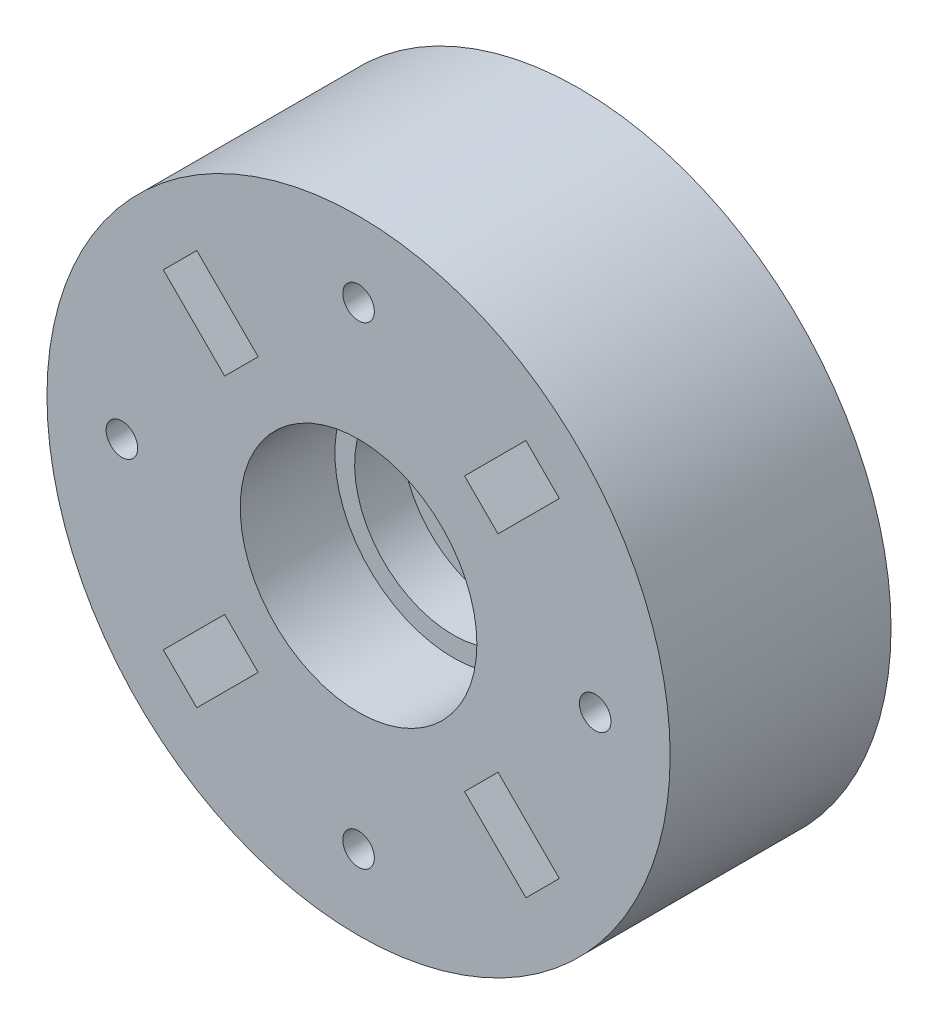
SolidWorks part; units mm, degrees
ref_plane "Alzado" through (0, 0, 0) normal (0, 0, 1) x (1, 0, 0)
ref_plane "Planta" through (0, 0, 0) normal (0, 1, 0) x (1, 0, 0)
ref_plane "Vista lateral" through (0, 0, 0) normal (1, 0, 0) x (0, 0, -1)
sketch "Croquis1" plane through (0, 0, 0) normal (0, 0, 1) x (1, 0, 0)
  line L0 (0, 50.6458) -> (0, -51.1293) construction
  circle A0 centre (0, 0) radius 39.5
  circle A1 centre (0, 0) radius 12.5
  circle A2 centre (0, 30) radius 2
  circle A3 centre (30, 0) radius 2
  circle A4 centre (0, -30) radius 2
  circle A5 centre (-30, 0) radius 2
  point P17 (0, 0)
  dimension "D1" = 79
  dimension "D2" = 25
  dimension "D4" = 4
  dimension "D3" = 30
  dimension "D5" = 4
extrude "Saliente-Extruir1" add sketch "Croquis1" along normal blind 28
sketch "Croquis3" plane through (0, 0, 28) normal (0, 0, 1) x (1, 0, 0)
  line L0 (0, 0) -> (28.2843, 28.2843) construction
  line L1 (0, 0) -> (39.5, 0) construction
  line L2 (17.6777, 13.435) -> (25.4558, 21.2132)
  line L3 (17.6777, 13.435) -> (13.435, 17.6777)
  line L4 (25.4558, 21.2132) -> (21.2132, 25.4558)
  line L5 (13.435, 17.6777) -> (21.2132, 25.4558)
  line L6 (17.6777, 13.435) -> (21.2132, 25.4558) construction
  line L7 (25.4558, 21.2132) -> (13.435, 17.6777) construction
  line L8 (13.435, -16.9706) -> (21.2132, -24.7487)
  line L9 (13.435, -16.9706) -> (17.6777, -12.7279)
  line L10 (17.6777, -12.7279) -> (25.4558, -20.5061)
  line L11 (21.2132, -24.7487) -> (25.4558, -20.5061)
  line L12 (-16.9706, -12.7279) -> (-24.7487, -20.5061)
  line L13 (-16.9706, -12.7279) -> (-12.7279, -16.9706)
  line L14 (-12.7279, -16.9706) -> (-20.5061, -24.7487)
  line L15 (-24.7487, -20.5061) -> (-20.5061, -24.7487)
  line L16 (-12.7279, 17.6777) -> (-20.5061, 25.4558)
  line L17 (-12.7279, 17.6777) -> (-16.9706, 13.435)
  line L18 (-16.9706, 13.435) -> (-24.7487, 21.2132)
  line L19 (-20.5061, 25.4558) -> (-24.7487, 21.2132)
  circle A0 centre (0, 0) radius 39.5 construction
  circle A1 centre (0, 0) radius 15
  point P8 (19.4454, 19.4454)
  point P27 (0.3536, 0.3536)
  dimension "D9" = 30
  dimension "D1" = 40
  dimension "D2" = 45
  dimension "D3" = 3
  dimension "D4" = 3
  dimension "D5" = 11
  dimension "D6" = 27.5
  dimension "D7" = 6
  dimension "D8" = 4
extrude "Cortar-Extruir1" cut sketch "Croquis3" against normal blind 12
sketch "Croquis5" plane through (0, 0, 0) normal (0, 0, -1) x (-1, 0, 0)
  circle A0 centre (0, 0) radius 16.8579
  dimension "D1" = 33.7158
extrude "Saliente-Extruir2" add sketch "Croquis5" against normal blind 10
sketch "Croquis4" plane through (0, 0, 0) normal (0, 0, -1) x (-1, 0, 0)
  line L0 (30, -3.5) -> (33.0311, -1.75)
  line L1 (3.5, 30) -> (1.75, 33.0311)
  line L2 (1.75, 33.0311) -> (-1.75, 33.0311)
  line L3 (-1.75, 33.0311) -> (-3.5, 30)
  line L4 (-3.5, 30) -> (-1.75, 26.9689)
  line L5 (-1.75, 26.9689) -> (1.75, 26.9689)
  line L6 (1.75, 26.9689) -> (3.5, 30)
  line L7 (33.0311, -1.75) -> (33.0311, 1.75)
  line L8 (33.0311, 1.75) -> (30, 3.5)
  line L9 (30, 3.5) -> (26.9689, 1.75)
  line L10 (26.9689, 1.75) -> (26.9689, -1.75)
  line L11 (26.9689, -1.75) -> (30, -3.5)
  line L12 (-3.5, -30) -> (-1.75, -33.0311)
  line L13 (-1.75, -33.0311) -> (1.75, -33.0311)
  line L14 (1.75, -33.0311) -> (3.5, -30)
  line L15 (3.5, -30) -> (1.75, -26.9689)
  line L16 (1.75, -26.9689) -> (-1.75, -26.9689)
  line L17 (-1.75, -26.9689) -> (-3.5, -30)
  line L18 (-30, 3.5) -> (-33.0311, 1.75)
  line L19 (-33.0311, 1.75) -> (-33.0311, -1.75)
  line L20 (-33.0311, -1.75) -> (-30, -3.5)
  line L21 (-30, -3.5) -> (-26.9689, -1.75)
  line L22 (-26.9689, -1.75) -> (-26.9689, 1.75)
  line L23 (-26.9689, 1.75) -> (-30, 3.5)
  line L24 (0, 0) -> (28.2843, 28.2843) construction
  line L25 (0, 0) -> (39.5, 0) construction
  line L26 (0.3536, -13.7886) -> (29.3449, 15.2028)
  line L27 (0.3536, -13.7886) -> (-13.7886, 0.3536)
  line L28 (29.3449, 15.2028) -> (15.2028, 29.3449)
  line L29 (-13.7886, 0.3536) -> (15.2028, 29.3449)
  line L30 (0.3536, -13.7886) -> (15.2028, 29.3449) construction
  line L31 (29.3449, 15.2028) -> (-13.7886, 0.3536) construction
  line L32 (25.1023, 25.1023) -> (18.7383, 31.4663) construction
  line L33 (25.1023, 25.1023) -> (28.9736, 21.231) construction
  line L34 (0, 0) -> (-15.8104, -15.8104) construction
  line L35 (-9.5459, -9.5459) -> (-4.5375, -14.5544) construction
  line L36 (-9.5459, -9.5459) -> (-14.3054, -4.7865) construction
  line L37 (21.9203, 28.2843) -> (-17.5609, -11.1969) construction
  line L38 (28.2843, 21.9203) -> (-9.2053, -15.5692) construction
  circle A0 centre (0, 30) radius 3.5 construction
  circle A1 centre (0, 0) radius 39.5 construction
  circle A3 centre (-12.7279, -6.364) radius 1.75
  circle A4 centre (-6.364, -12.7279) radius 1.75
  circle A5 centre (21.9203, 28.2843) radius 1.75
  circle A6 centre (28.2843, 21.9203) radius 1.75
  point P30 (0, 0)
  point P36 (7.7782, 7.7782)
  dimension "D11" = 3.5
  dimension "D12" = 3.5
  dimension "D13" = 3.5
  dimension "D14" = 3.5
  dimension "D1" = 4
  dimension "D2" = 40
  dimension "D3" = 45
  dimension "D4" = 20
  dimension "D5" = 10
  dimension "D6" = 9.5
  dimension "D7" = 4.5
  dimension "D8" = 4.5
  dimension "D9" = 4
  dimension "D10" = 4
extrude "Cortar-Extruir2" cut sketch "Croquis4" against normal blind 10
